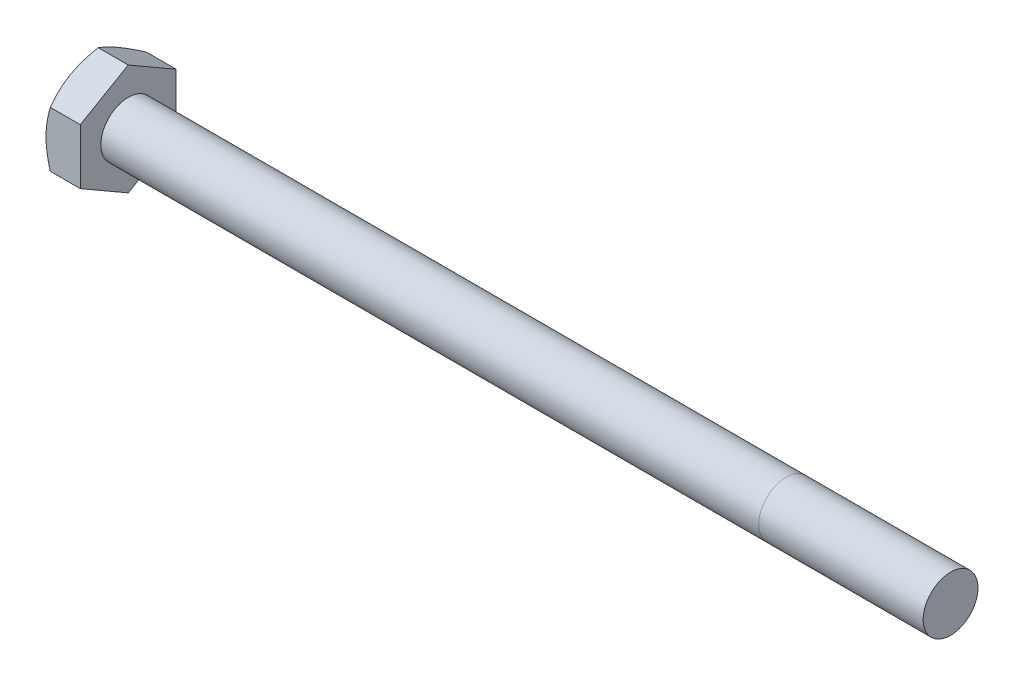
SolidWorks part; units mm, degrees
material "Alloy Steel"
ref_plane "Front Plane" through (0, 0, 0) normal (0, 0, 1) x (1, 0, 0)
ref_plane "Top Plane" through (0, 0, 0) normal (0, 1, 0) x (1, 0, 0)
ref_plane "Right Plane" through (0, 0, 0) normal (1, 0, 0) x (0, 0, -1)
sketch "Sketch1" plane through (0, 0, 0) normal (0, 0, 1) x (1, 0, 0)
  line L0 (-49.6094, 0) -> (49.6094, 0) construction
  line L1 (49.6094, 3.175) -> (49.6094, -3.175) construction
  line L2 (-45.6406, 5.5562) -> (-45.6406, -5.5562) construction
  line L3 (-49.6094, 5.5562) -> (-49.6094, -5.5562) construction
  point P9 (-45.6406, 0)
  point P10 (45.1644, -3.175)
  dimension "D1" = 4.445
  dimension "Screw Dia" = 6.35
  dimension "Hex" = 11.1125
  dimension "Head Ht" = 3.9688
  dimension "Screw Lenght" = 95.25
ref_plane "Plane2" through (49.6094, 0, 0) normal (1, 0, 0) x (0, 0, -1)
sketch "Sketch5" plane through (49.6094, 0, 0) normal (1, 0, 0) x (0, 0, -1)
  circle A0 centre (0, 0) radius 3.175
extrude "Boss-Extrude3" add sketch "Sketch5" against normal up to vertex (95.25 mm away) up to point (-45.6406, 0, 0)
sketch "Sketch9" plane through (49.6094, 0, 0) normal (1, 0, 0) x (0, 0, -1)
  circle A1 centre (0, 0) radius 3.175
  circle A2 centre (0, 0) radius 3.175
  dimension "D1" = 0
curve "Helix/Spiral1" pitch 1.27 height 20.32 turns 16 parameters "Pitch"=1.27
chamfer "Chamfer1" [suppressed] distance 0.9525 angle 45
sketch "Sketch10" plane through (0, 0, 0) normal (0, 0, 1) x (1, 0, 0)
  line L0 (49.6094, 3.175) -> (50.0856, 2.3501)
  line L1 (50.0856, 2.3501) -> (50.2444, 2.3501)
  line L2 (50.2444, 2.3501) -> (50.7206, 3.175)
  line L3 (49.6094, 3.175) -> (50.7206, 3.175)
  line L4 (50.165, 3.175) -> (50.165, 2.3501) construction
  line L5 (49.8475, 2.7626) -> (50.4825, 2.7626) construction
  dimension "D1" = 60
  dimension "D2" = 0.1588
  dimension "D3" = 0.635
sweep "Cut-Sweep1" [suppressed] cut profiles "Sketch10" path "Helix/Spiral1"
sketch "Sketch11" plane through (0, 0, 0) normal (0, 0, 1) x (1, 0, 0)
  line L0 (-45.6406, 3.175) -> (-45.6406, 0)
  line L1 (-45.6406, 0) -> (33.7344, 0)
  line L3 (33.7344, 0) -> (30.5594, 3.175)
  line L4 (-45.6406, 3.175) -> (30.5594, 3.175)
  dimension "D1" = 45
  dimension "MIn Thread" = 19.05
revolve "Revolve1" add sketch "Sketch11" angle 360 about L1
sketch "Sketch6" plane through (-45.6406, 0, 0) normal (-1, 0, 0) x (0, 0, 1)
  line L0 (0, 5.5562) -> (0, -5.5562) construction
  line L1 (5.5563, 3.2079) -> (0, 6.4158)
  line L2 (0, 6.4158) -> (-5.5562, 3.2079)
  line L3 (-5.5562, 3.2079) -> (-5.5562, -3.2079)
  line L4 (-5.5562, -3.2079) -> (0, -6.4158)
  line L5 (0, -6.4158) -> (5.5563, -3.2079)
  line L6 (5.5563, -3.2079) -> (5.5563, 3.2079)
  circle A0 centre (0, 0) radius 5.5563 construction
extrude "Boss-Extrude4" add sketch "Sketch6" along normal up to vertex (3.9688 mm away) up to point (-49.6094, -5.5562, 0)
sketch "Sketch7" plane through (-49.6094, 0, 0) normal (-1, 0, 0) x (0, 0, 1)
  circle A0 centre (0, 0) radius 5.5563 construction
  circle A1 centre (0, 0) radius 5.5563
sketch "Sketch8" plane through (-49.6094, 0, 0) normal (-1, 0, 0) x (0, 0, 1)
  circle A0 centre (0, 0) radius 5.5563 construction
  circle A1 centre (0, 0) radius 5.5563
extrude "Cut-Extrude3" cut sketch "Sketch8" against normal through all draft 60 flip side to cut
sketch "Sketch12" plane through (-49.6094, 0, 0) normal (-1, 0, 0) x (0, 0, 1)
  line L0 (0, 4.2783) -> (0, 2.3892) construction
  line L1 (0.1667, 4.2783) -> (0.1667, 2.3892)
  line L2 (-0.1667, 4.2783) -> (-0.1667, 2.3892)
  line L3 (0, 3.175) -> (0, -3.175) construction
  arc A0 (0.1667, 4.2783) -> (-0.1667, 4.2783) centre (0, 4.2783) ccw
  arc A1 (-0.1667, 2.3892) -> (0.1667, 2.3892) centre (0, 2.3892) ccw
  circle A3 centre (0, 0) radius 2.2225 construction
  circle A4 centre (0, 0) radius 4.445 construction
  point P2 (0, 3.3337)
  dimension "D1" = 4.445
  dimension "D3" = 8.89
  dimension "D2" = 0.3334
extrude "Cut-Extrude4" cut sketch "Sketch12" against normal blind 0.254
pattern_circular "CirPattern1" count 3 over 360 about axis through (-45.6406, 0, 0) along (1, 0, 0) of "Cut-Extrude4"
sketch "Sketch13" plane through (0, 0, 0) normal (0, 1, 0) x (1, 0, 0)
  line L0 (30.5594, -3.175) -> (30.5594, 3.175)
  line L1 (-45.6406, -3.175) -> (49.6094, -3.175) construction
  line L2 (49.6094, 3.175) -> (-45.6406, 3.175) construction
  line L3 (49.6094, -3.175) -> (49.6094, 3.175) construction
  point P8 (30.5594, 0)
  dimension "D1" = 19.05
split line "Split Line4"
equation "\"D2@Sketch10\" = \"Pitch@Helix/Spiral1\"*.125"
equation "\"D3@Sketch10\" = \"Pitch@Helix/Spiral1\"*.5"
equation "\"D3@Helix/Spiral1\" = \"MIn Thread@Sketch11\"+\"Pitch@Helix/Spiral1\""
equation "\"D1@Chamfer1\" = \"Pitch@Helix/Spiral1\"*.75"
equation "\"D1@Sketch12\" = \"Hex@Sketch1\"*.4"
equation "\"D3@Sketch12\" = \"Hex@Sketch1\"*.8"
equation "\"D2@Sketch12\" = \"Hex@Sketch1\"*.03"
equation "\"D1@Sketch1\" = \"Pitch@Helix/Spiral1\"*3.5"
